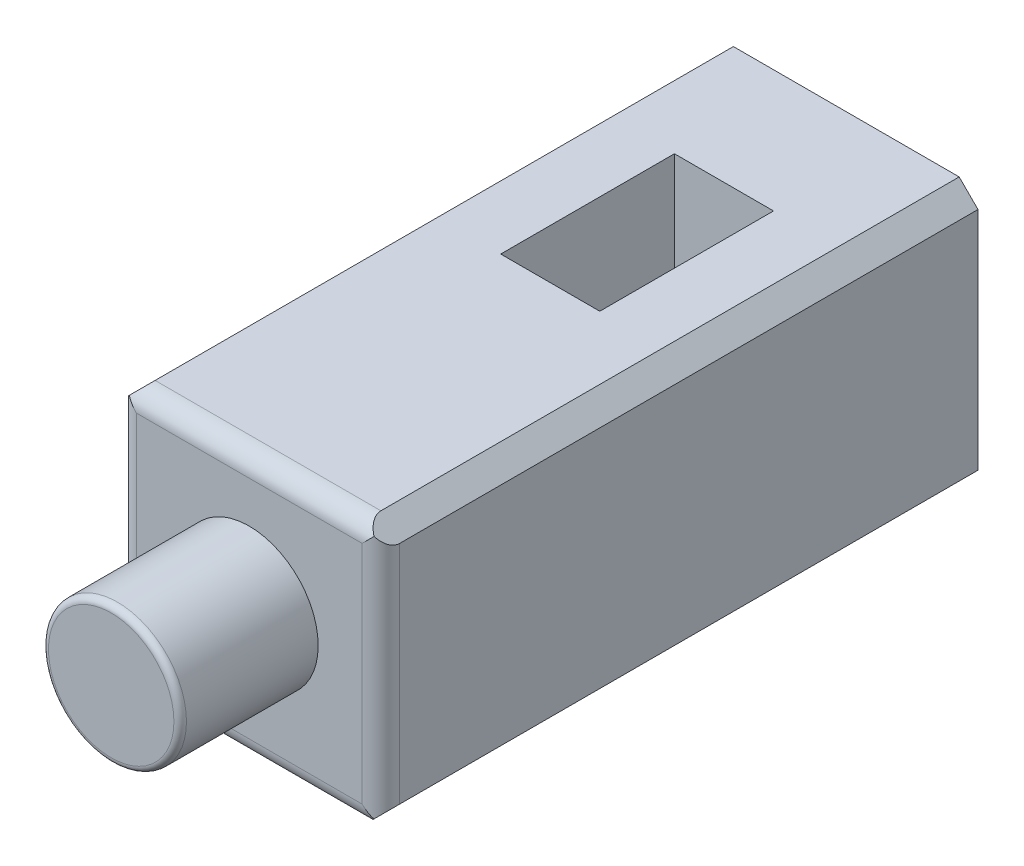
SolidWorks part; units mm, degrees
ref_plane "Front Plane" through (0, 0, 0) normal (0, 0, 1) x (1, 0, 0)
ref_plane "Top Plane" through (0, 0, 0) normal (0, 1, 0) x (1, 0, 0)
ref_plane "Right Plane" through (0, 0, 0) normal (1, 0, 0) x (0, 0, -1)
sketch "Sketch1" plane through (0, 0, 0) normal (0, 0, 1) x (1, 0, 0)
  line L1 (-21, -21) -> (21, -21)
  line L2 (-21, -21) -> (-21, 21)
  line L3 (-21, 21) -> (21, 21)
  line L4 (21, -21) -> (21, 21)
  line L5 (-21, -21) -> (21, 21) construction
  line L6 (-21, 21) -> (21, -21) construction
  point P0 (0, 0)
  dimension "D1" = 42
  dimension "D2" = 42
extrude "Boss-Extrude1" add sketch "Sketch1" along normal blind 95.2
sketch "Sketch2" plane through (0, 0, 95.2) normal (0, 0, 1) x (1, 0, 0)
  circle A0 centre (0, 0.3931) radius 11
  dimension "D1" = 22
extrude "Boss-Extrude2" add sketch "Sketch2" along normal blind 22
sketch "Sketch3" plane through (0, 21, 0) normal (0, 1, 0) x (1, 0, 0)
  line L0 (21, 0) -> (-21, 0) construction
  line L1 (-7.9, -47.2) -> (7.9, -47.2)
  line L2 (-7.9, -47.2) -> (-7.9, -19.5)
  line L3 (-7.9, -19.5) -> (7.9, -19.5)
  line L4 (7.9, -47.2) -> (7.9, -19.5)
  line L5 (-7.9, -47.2) -> (7.9, -19.5) construction
  line L6 (-7.9, -19.5) -> (7.9, -47.2) construction
  point P0 (0, -33.35)
  dimension "D1" = 15.8
  dimension "D2" = 27.7
  dimension "D3" = 19.5
extrude "Cut-Extrude1" cut sketch "Sketch3" against normal blind 21
sketch "Sketch4" plane through (0, 0, 0) normal (0, 0, -1) x (-1, 0, 0)
  circle A0 centre (0, 0) radius 5
  dimension "D1" = 10
extrude "Cut-Extrude2" cut sketch "Sketch4" against normal blind 10
chamfer "Chamfer1" distance 3 angle 45 4 edges at (-21, -21, 47.6) (-21, 21, 47.6) (21, -21, 47.6) (21, 21, 47.6)
fillet "Fillet1" radius 3 4 edges at (-21, 0, 95.2) (0, -21, 95.2) (21, 0, 95.2) (0, 21, 95.2)
fillet "Fillet2" radius 1 1 edges at (11, 0.3931, 117.2)
